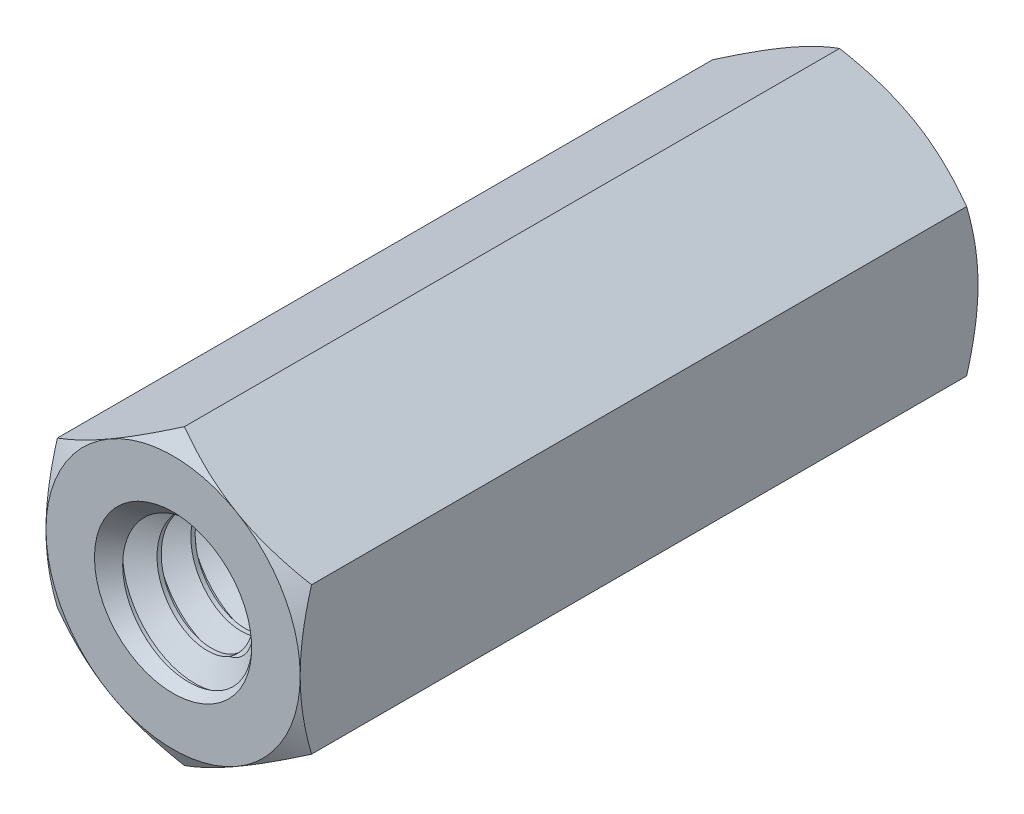
SolidWorks part; units mm, degrees
material "1060 Alloy"
ref_plane "Front Plane" through (0, 0, 0) normal (0, 0, 1) x (1, 0, 0)
ref_plane "Top Plane" through (0, 0, 0) normal (0, 1, 0) x (1, 0, 0)
ref_plane "Right Plane" through (0, 0, 0) normal (1, 0, 0) x (0, 0, -1)
sketch "Sketch3" plane through (0, 0, 0) normal (1, 0, 0) x (0, 0, -1)
  line L0 (-6.35, 0) -> (6.35, 0) construction
  line L1 (0, 2.3813) -> (0, -2.3813) construction
  line L2 (-6.35, 1.4224) -> (-6.35, -1.4224) construction
  point P2 (-6.35, 0)
  point P3 (6.35, 0)
  dimension "Length" = 12.7
  dimension "Min Thread Length" = 12.7
  dimension "D1" = 12.7
  dimension "Thread Dia" = 2.8448
  dimension "Hex" = 4.7625
sketch "Sketch1" plane through (0, 0, 0) normal (0, 0, 1) x (1, 0, 0)
  line L1 (0, 2.7496) -> (-2.3813, 1.3748)
  line L2 (-2.3813, 1.3748) -> (-2.3813, -1.3748)
  line L3 (-2.3813, -1.3748) -> (0, -2.7496)
  line L4 (0, -2.7496) -> (2.3813, -1.3748)
  line L5 (2.3813, -1.3748) -> (2.3812, 1.3748)
  line L6 (2.3812, 1.3748) -> (0, 2.7496)
  circle A0 centre (0, 0) radius 2.3813 construction
  circle A1 centre (0, 0) radius 1.4224
extrude "Extrude1" add sketch "Sketch1" along normal up to vertex (6.35 mm away) and the other way up to vertex (6.35 mm away) up to point (0, 0, 6.35) other way up to point (0, 0, -6.35)
sketch "Sketch11" plane through (0, 0, -6.35) normal (0, 0, -1) x (-1, 0, 0)
  circle A0 centre (0, 0) radius 1.4224 construction
  circle A1 centre (0, 0) radius 1.4224
curve "Helix/Spiral1" pitch 0.635 height 13.335 radius 1.4224 centre (0, 0, -6.35) axis (0, 0, 1) start towards (0, 1, 0) parameters "Pitch"=0.635
sketch "Sketch12" plane through (0, 0, 0) normal (1, 0, 0) x (0, 0, -1)
  line L0 (6.9056, 1.4224) -> (6.35, 1.4224)
  line L1 (6.9056, 1.4224) -> (6.6675, 1.01)
  line L2 (6.6675, 1.01) -> (6.5881, 1.01)
  line L3 (6.5881, 1.01) -> (6.35, 1.4224)
  line L4 (6.6278, 1.01) -> (6.6278, 1.4224) construction
  line L5 (6.7866, 1.2162) -> (6.4691, 1.2162) construction
  dimension "D1" = 0.0794
  dimension "D2" = 0.3175
  dimension "D3" = 60
sweep "Sweep1" add profiles "Sketch12" path "Helix/Spiral1"
sketch "Sketch6" plane through (0, 0, -6.35) normal (0, 0, -1) x (-1, 0, 0)
  line L6 (0, 2.7496) -> (-2.3812, 1.3748)
  line L7 (-2.3812, 1.3748) -> (-2.3813, -1.3748)
  line L8 (-2.3813, -1.3748) -> (0, -2.7496)
  line L9 (0, -2.7496) -> (2.3813, -1.3748)
  line L10 (2.3813, -1.3748) -> (2.3813, 1.3748)
  line L11 (2.3813, 1.3748) -> (0, 2.7496)
  line L12 (0, 2.7496) -> (-2.3812, 1.3748)
  line L13 (-2.3812, 1.3748) -> (-2.3813, -1.3748)
  line L14 (-2.3813, -1.3748) -> (0, -2.7496)
  line L15 (0, -2.7496) -> (2.3813, -1.3748)
  line L16 (2.3813, -1.3748) -> (2.3813, 1.3748)
  line L17 (2.3813, 1.3748) -> (0, 2.7496)
  dimension "D1" = 0
extrude "Extrude2" cut sketch "Sketch6" along normal through all
sketch "Sketch7" plane through (0, 0, -6.35) normal (0, 0, -1) x (-1, 0, 0)
  circle A2 centre (0, 0) radius 1.4732
  circle A3 centre (0, 0) radius 1.4732
  dimension "D1" = 0.0508
extrude "Extrude3" cut sketch "Sketch7" against normal through all draft 43
sketch "Sketch8" plane through (0, 0, -6.35) normal (0, 0, -1) x (-1, 0, 0)
  circle A0 centre (0, 0) radius 2.3813 construction
  circle A1 centre (0, 0) radius 2.3813
extrude "Extrude4" cut sketch "Sketch8" against normal through all draft 60 flip side to cut
mirror "Mirror1" about plane through (0, 0, 0) normal (0, 0, 1) of "Extrude2", "Extrude3", "Extrude4"
sketch "Sketch9" [suppressed] plane through (0, 0, 0) normal (1, 0, 0) x (0, 0, -1)
  line L1 (-12.7, 2.4638) -> (12.7, 2.4638)
  line L2 (-12.7, 2.4638) -> (-12.7, 0)
  line L3 (-12.7, 0) -> (12.7, 0)
  line L4 (12.7, 2.4638) -> (12.7, 0)
  line L7 (-25.4, 0) -> (25.4, 0) construction
revolve "Revolve" [suppressed] add sketch "Sketch9" angle 360 about L0
sketch "Sketch10" [suppressed] plane through (0, 0, 0) normal (1, 0, 0) x (0, 0, -1)
  line L0 (25.4, 2.413) -> (12.7, 2.413)
  line L1 (-25.4, 2.413) -> (-12.7, 2.413)
  line L2 (12.7, 2.413) -> (12.7, -2.413)
  line L3 (-25.4, -2.4638) -> (-12.7, -2.4638)
  line L4 (-12.7, 2.413) -> (-12.7, -2.4638)
  line L5 (12.7, -2.413) -> (25.4, -2.413)
equation "\"D1@Sketch3\" = \"Min Thread Length@Sketch3\""
equation "\"D3@Helix/Spiral1\" = \"Length@Sketch3\"+\"Pitch@Helix/Spiral1\""
equation "\"D1@Sketch12\" = \"Pitch@Helix/Spiral1\"*.125"
equation "\"D2@Sketch12\" = \"Pitch@Helix/Spiral1\"*.5"
